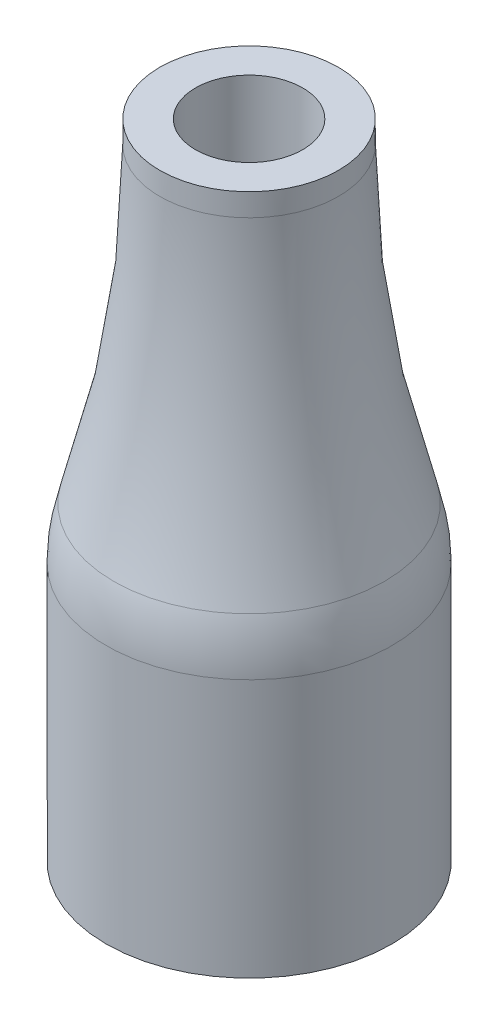
SolidWorks part; units mm, degrees
ref_plane "Front Plane" through (0, 0, 0) normal (0, 0, 1) x (1, 0, 0)
ref_plane "Top Plane" through (0, 0, 0) normal (0, 1, 0) x (1, 0, 0)
ref_plane "Right Plane" through (0, 0, 0) normal (1, 0, 0) x (0, 0, -1)
sketch "Sketch1" plane through (0, 0, 0) normal (0, 1, 0) x (1, 0, 0)
  circle A0 centre (0, 0) radius 4
  dimension "D1" = 8
extrude "Boss-Extrude4" add sketch "Sketch1" along normal blind 8
sketch "Sketch6" plane through (0, 8, 0) normal (0, 1, 0) x (1, 0, 0)
  circle A0 centre (0, 0) radius 2.5
  dimension "D1" = 5
extrude "Boss-Extrude5" add sketch "Sketch6" along normal blind 10
fillet "Fillet1" radius 30 1 edges at (0, 8, 2.5)
fillet "Fillet2" radius 5 1 edges at (0, 8, 4)
shell "Shell4" thickness 1.5 removed face at (0, 0, 4)
sketch "Sketch8" plane through (0, 18, 0) normal (0, 1, 0) x (1, 0, 0)
  circle A0 centre (0, 0) radius 1.5
  dimension "D1" = 3
extrude "Cut-Extrude2" cut sketch "Sketch8" against normal blind 18
thread "Thread1" pitch 1 method cut profile "Thread Profile1" start angle 0, offset 1.4, length 0, pitch 1, diameter 5
ref_plane "Plane1" through (2.5, -1.4, 0) normal (0, 0, 1) x (1, 0, 0)
sketch "Thread Profile1" plane through (2.5, -1.4, 0) normal (0, 0, 1) x (1, 0, 0)
  line L0 (0, 0) -> (0, 1) construction
  line L1 (0, 0) -> (0.5413, 0.3125)
  line L2 (0.5413, 0.3125) -> (0.5413, 0.4375)
  line L3 (0.5413, 0.4375) -> (0, 0.75)
  line L4 (0.5413, 0.375) -> (0, 0.375) construction
  line L11 (0, 0) -> (0, 0.75)
  point P2 (0, 0)
  dimension "Pitch" = 1
  dimension "Profile_Angle" = 60
  dimension "Profile_Land" = 0.125
  dimension "Profile_Height" = 0.5413
sketch "Sketch11" plane through (0, 0, 0) normal (0, -1, 0) x (1, 0, 0)
  circle A0 centre (0, 0) radius 3.5
  dimension "D1" = 7
extrude "Cut-Extrude3" cut sketch "Sketch11" against normal blind 0.5
fillet "Fillet4" radius 1 1 edges at (0, 0.5, -3.5)
